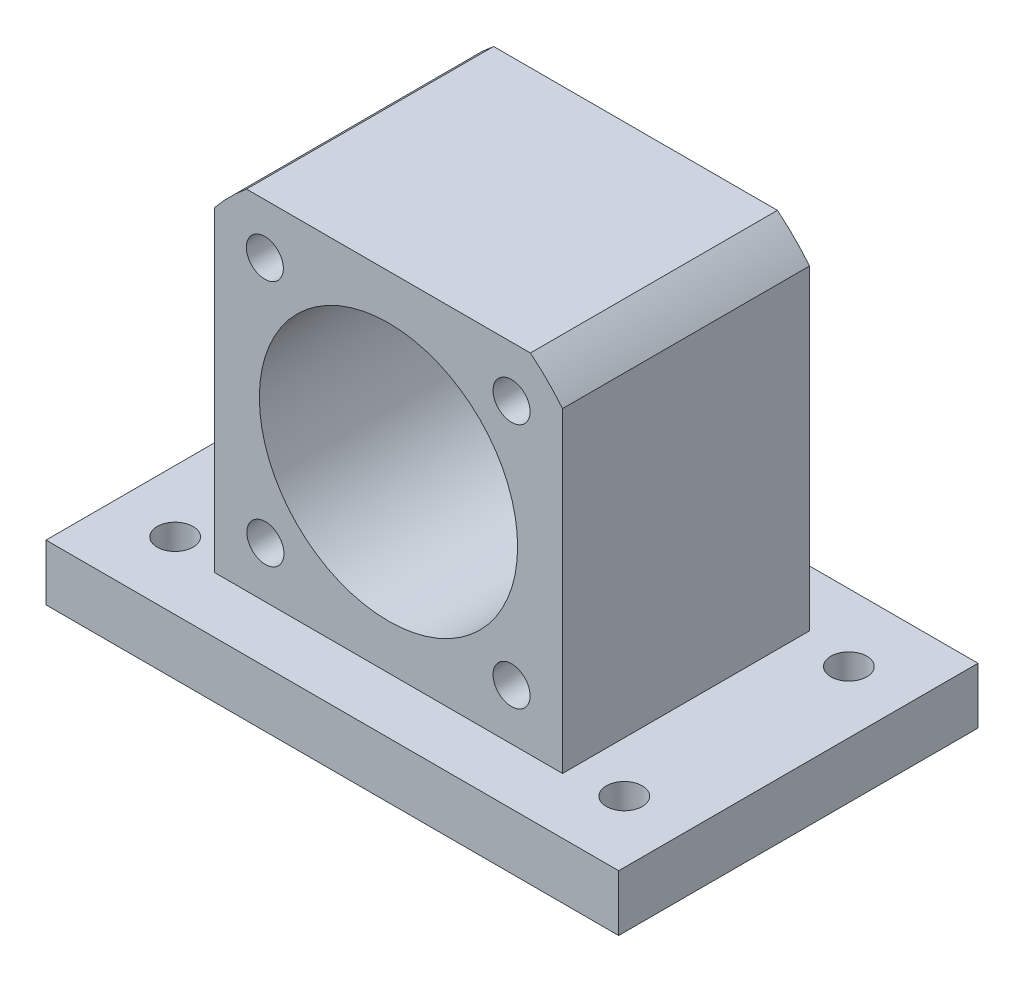
SolidWorks part; units mm, degrees
ref_plane "前视基准面" through (0, 0, 0) normal (0, 0, 1) x (1, 0, 0)
ref_plane "上视基准面" through (0, 0, 0) normal (0, 1, 0) x (1, 0, 0)
ref_plane "右视基准面" through (0, 0, 0) normal (1, 0, 0) x (0, 0, -1)
sketch "草图1" plane through (0, 0, 0) normal (0, 0, 1) x (1, 0, 0)
  line L1 (15.5, -15.5) -> (-15.5, -15.5)
  line L2 (15.5, -15.5) -> (15.5, 12.6392)
  line L3 (12.6392, 15.5) -> (-12.6392, 15.5)
  line L4 (-15.5, -15.5) -> (-15.5, 12.6392)
  line L5 (15.5, -15.5) -> (-15.5, 15.5) construction
  line L6 (15.5, 15.5) -> (-15.5, -15.5) construction
  arc A1 (-12.6392, 15.5) -> (-15.5, 12.6392) centre (0, 0) ccw
  arc A3 (15.5, 12.6392) -> (12.6392, 15.5) centre (0, 0) ccw
  point P0 (0, 0)
  dimension "D3" = 40
  dimension "D1" = 31
  dimension "D2" = 31
  dimension "D4" = 15.5
extrude "凸台-拉伸1" add sketch "草图1" along normal mid plane 22
sketch "草图2" plane through (0, 0, 11) normal (0, 0, 1) x (1, 0, 0)
  circle A0 centre (0, 0) radius 11.5
  dimension "D1" = 23
extrude "切除-拉伸1" cut sketch "草图2" against normal up to next
sketch "草图3" plane through (0, 0, 11) normal (0, 0, 1) x (1, 0, 0)
  line L0 (15.5, -15.5) -> (-11.8567, 11.8567)
  line L1 (-15.5, -15.5) -> (12.4691, 12.4691)
  circle A0 centre (0, 0) radius 15.5
  point P9 (-11.0121, 11.0121)
  point P10 (10.9602, 10.9602)
  dimension "D1" = 31
hole_wizard "M4 螺纹孔1" positions "草图4" profile "草图5" tap size "M4" standard "GB"
sketch "草图4" plane through (0, 0, 11) normal (0, 0, 1) x (1, 0, 0)
  line L0 (15.5, -15.5) -> (-11.8567, 11.8567) construction
  line L1 (-15.5, -15.5) -> (12.4691, 12.4691) construction
  circle A0 centre (0, 0) radius 15.5 construction
  point P0 (-11.0121, 11.0121)
  point P3 (10.9602, 10.9602)
  point P6 (10.9602, -10.9602)
  point P12 (-10.9602, -10.9602)
sketch "草图5" plane through (-11.0121, 11.0121, 11) normal (1, 0, 0) x (0, -1, 0)
  line L0 (0, 0) -> (0, 11.0914)
  line L1 (0, 11.0914) -> (1.65, 10.1)
  line L2 (1.65, 10.1) -> (1.65, 0)
  line L5 (1.65, 0) -> (0, 0)
  line L10 (0, 11.0914) -> (-1.65, 10.1) construction
  line L11 (0, -6.35) -> (0, 107.95) construction
  dimension "螺纹孔钻头直径" = 3.3
  dimension "螺纹孔钻头深度" = 10.1
  dimension "导头角度" = 118
sketch "草图9" plane through (0, -15.5, 0) normal (0, -1, 0) x (1, 0, 0)
  line L0 (-15.5, 11) -> (-15.5, -11) construction
  line L5 (25.5, -16) -> (-25.5, -16)
  line L6 (25.5, -16) -> (25.5, 16)
  line L7 (25.5, 16) -> (-25.5, 16)
  line L8 (-25.5, -16) -> (-25.5, 16)
  line L9 (25.5, -16) -> (-25.5, 16) construction
  line L10 (25.5, 16) -> (-25.5, -16) construction
  line L11 (-15.5, 11) -> (15.5, 11) construction
  point P0 (0, 0)
  dimension "D1" = 10
  dimension "D2" = 5
extrude "凸台-拉伸2" add sketch "草图9" along normal blind 5
sketch "草图10" plane through (0, -20.5, 0) normal (0, -1, 0) x (1, 0, 0)
  point P0 (-20, 10)
  point P1 (-20, -10)
  point P2 (20, -10)
  point P3 (20, 10)
  dimension "D1" = 40
  dimension "D2" = 40
  dimension "D3" = 20
  dimension "D4" = 20
  dimension "D5" = 20
  dimension "D6" = 20
  dimension "D7" = 10
  dimension "D8" = 10
hole_wizard "Ø3.2 (3.2) 直径孔1" positions "草图11" profile "草图12" hole size "Ø3.2" standard "GB" end condition up to next
sketch "草图11" plane through (0, -20.5, 0) normal (0, -1, 0) x (-1, 0, 0)
  point P0 (20, -10)
  point P3 (-20, -10)
  point P6 (-20, 10)
  point P9 (20, 10)
sketch "草图12" plane through (-20, -20.5, 10) normal (1, 0, 0) x (0, 0, -1)
  line L0 (0, 0) -> (0, 5)
  line L1 (0, 5) -> (1.6, 5)
  line L2 (1.6, 5) -> (1.6, 0)
  line L5 (1.6, 0) -> (0, 0)
  line L11 (0, -6.35) -> (0, 107.95) construction
  dimension "通孔孔直径" = 3.2
  dimension "通孔孔深度" = 5
